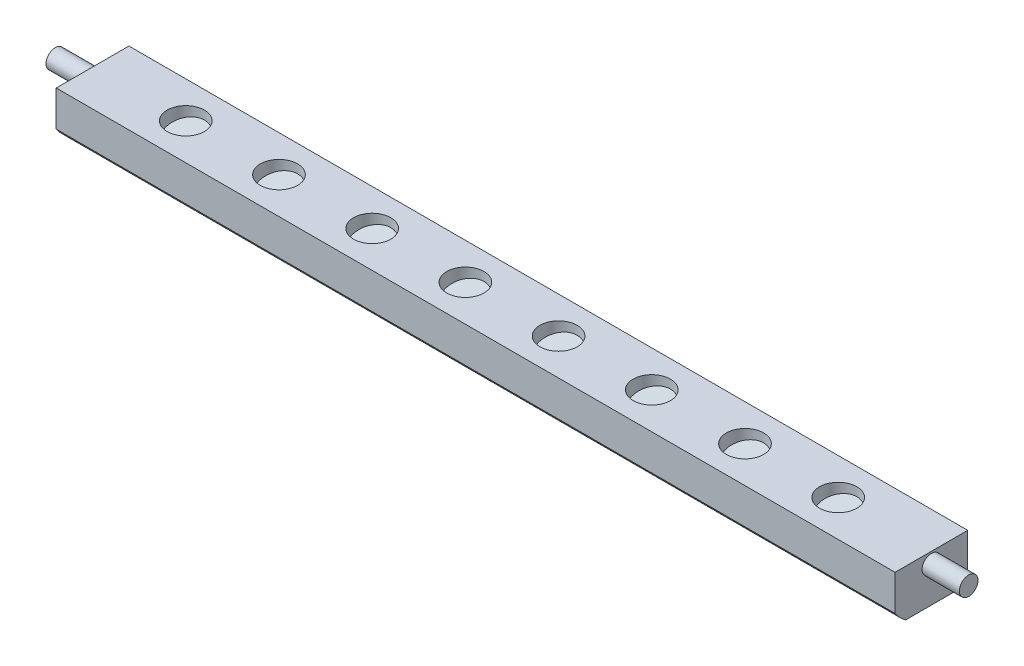
SolidWorks part; units mm, degrees
material "1023 Carbon Steel Sheet (SS)"
ref_plane "Front Plane" through (0, 0, 0) normal (0, 0, 1) x (1, 0, 0)
ref_plane "Top Plane" through (0, 0, 0) normal (0, 1, 0) x (1, 0, 0)
ref_plane "Right Plane" through (0, 0, 0) normal (1, 0, 0) x (0, 0, -1)
sketch "Sketch1" plane through (0, 0, 0) normal (0, 0, 1) x (1, 0, 0)
  line L1 (225, -10) -> (-225, -10)
  line L2 (225, -10) -> (225, 10)
  line L3 (225, 10) -> (-225, 10)
  line L4 (-225, -10) -> (-225, 10)
  line L5 (225, -10) -> (-225, 10) construction
  line L6 (225, 10) -> (-225, -10) construction
  point P0 (0, 0)
  dimension "D1" = 450
  dimension "D2" = 20
extrude "Boss-Extrude1" add sketch "Sketch1" along normal mid plane 28
sketch "Sketch2" plane through (0, 10, 0) normal (0, 1, 0) x (1, 0, 0)
  line L0 (-225, -14) -> (-225, 14) construction
  circle A0 centre (-175, 0) radius 10
  dimension "D1" = 20
  dimension "D2" = 50
extrude "Cut-Extrude1" cut sketch "Sketch2" against normal blind 10
pattern_linear "LPattern1" count 8 spacing 50 along (1, 0, 0) of "Cut-Extrude1"
sketch "Sketch3" plane through (225, 0, 0) normal (1, 0, 0) x (0, 0, -1)
  line L1 (-14, -10) -> (14, -10) construction
  circle A0 centre (0, 4) radius 5
  dimension "D1" = 10
  dimension "D2" = 14
extrude "Boss-Extrude2" add sketch "Sketch3" along normal blind 20
mirror "Mirror1" about plane through (0, 0, 0) normal (1, 0, 0) of "Boss-Extrude2"
fillet "Fillet1" radius 14 2 edges at (0, -10, 14) (0, -10, -14)
sketch "Sketch5" plane through (-225, 0, 0) normal (-1, 0, 0) x (0, 0, 1)
  line L0 (10, 0) -> (-10, 0) construction
  line L1 (10, 0) -> (-10, 0)
  line L5 (10, 0) -> (-10, 5.359)
  line L7 (-10, 0) -> (-10, 5.359)
  dimension "D1" = 15
  dimension "D2" = 20
extrude "Boss-Extrude3" add sketch "Sketch5" against normal up to surface (450 mm away) up to face at (225, 4, -5)
sketch "Sketch6" plane through (0, 0, 0) normal (1, 0, 0) x (0, 0, -1)
  line L0 (-14, 10) -> (14, 10) construction
  line L1 (-19.5, 10) -> (-14, 10)
  line L2 (19.5, 10) -> (19.5, -15)
  line L3 (19.5, -15) -> (-13.8293, -15)
  line L4 (-19.5, 10) -> (-19.5, -9.1149)
  line L5 (-14, 10) -> (-14, 4) construction
  line L6 (14, 10) -> (14, 4) construction
  line L7 (-14, 10) -> (-14, 4)
  line L8 (14, 10) -> (14, 4)
  line L9 (14, 10) -> (19.5, 10)
  arc A0 (-14, 4) -> (0, -10) centre (0, 4) ccw construction
  arc A1 (0, -10) -> (14, 4) centre (0, 4) ccw construction
  arc A2 (-14, 4) -> (0, -10) centre (0, 4) ccw
  arc A3 (0, -10) -> (14, 4) centre (0, 4) ccw
  arc A5 (-19.5, -9.1149) -> (-13.8293, -15) centre (0, 4) ccw
  dimension "D4" = 47
  dimension "D1" = 19.5
  dimension "D2" = 39
  dimension "D3" = 25
extrude "Boss-Extrude4" add sketch "Sketch6" against normal up to surface and the other way up to surface up to face at (-225, 4, -5) other way up to face at (225, 4, -5)
ref_axis "Axis1" through (-245, 4, 0) along (1, 0, 0)
ref_plane "Plane1" through (0, 4, 0) normal (0, -1, 0) x (1, 0, 0)
